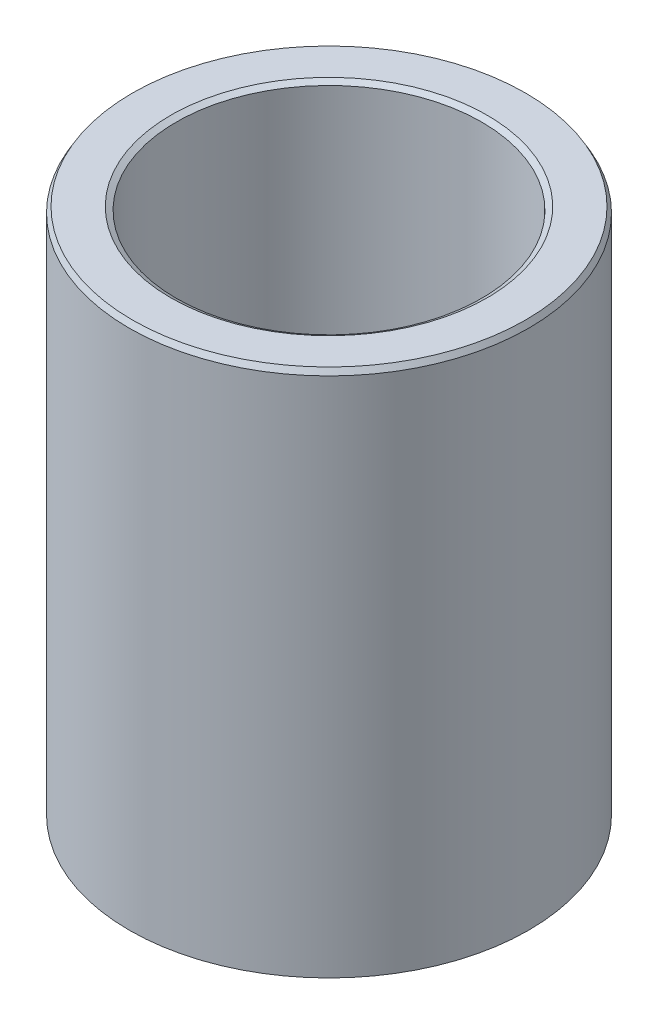
SolidWorks part; units mm, degrees
ref_plane "Front Plane" through (0, 0, 0) normal (0, 0, 1) x (1, 0, 0)
ref_plane "Top Plane" through (0, 0, 0) normal (0, 1, 0) x (1, 0, 0)
ref_plane "Right Plane" through (0, 0, 0) normal (1, 0, 0) x (0, 0, -1)
sketch "Sketch1" plane through (0, 0, 0) normal (0, 1, 0) x (1, 0, 0)
  circle A0 centre (0, 0) radius 17.5
  dimension "SLEEVE_OD" = 35
extrude "Boss-Extrude1" add sketch "Sketch1" along normal blind 46.4336
sketch "Sketch2" plane through (0, 0, 0) normal (0, 1, 0) x (1, 0, 0)
  circle A0 centre (0, 0) radius 13.3791
  dimension "BORE_D" = 26.7581
extrude "Cut-Extrude1" cut sketch "Sketch2" along normal through all
chamfer "Chamfer1" distance 0.4809 angle 30 4 edges at (0, 46.4336, 13.3791) (0, 0, 13.3791) (0, 0, 17.5) (0, 46.4336, 17.5) first distance on face at (0, 46.4336, 13.3791) first distance on face at (0, 0, 13.3791) first distance on face at (0, 46.4336, 17.5)
